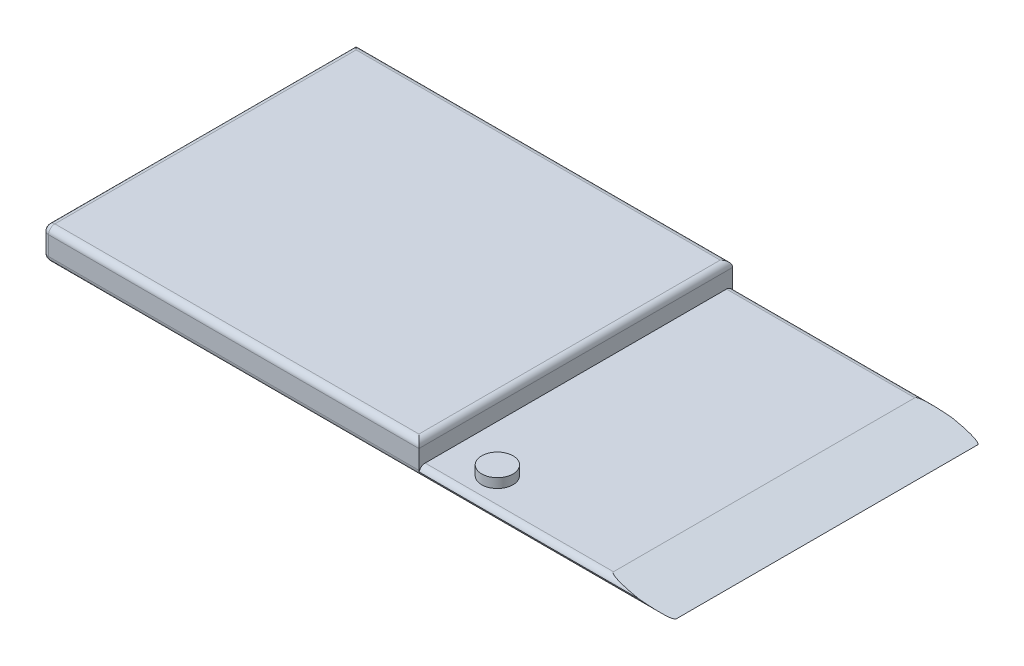
SolidWorks part; units mm, degrees
ref_plane "Front Plane" through (0, 0, 0) normal (0, 0, 1) x (1, 0, 0)
ref_plane "Top Plane" through (0, 0, 0) normal (0, 1, 0) x (1, 0, 0)
ref_plane "Right Plane" through (0, 0, 0) normal (1, 0, 0) x (0, 0, -1)
sketch "Sketch1" plane through (0, 0, 0) normal (0, 1, 0) x (1, 0, 0)
  line L1 (-127, 63.5) -> (127, 63.5)
  line L2 (-127, 63.5) -> (-127, -63.5)
  line L3 (-127, -63.5) -> (127, -63.5)
  line L4 (127, 63.5) -> (127, -63.5)
  line L5 (-127, 63.5) -> (127, -63.5) construction
  line L6 (-127, -63.5) -> (127, 63.5) construction
  point P0 (0, 0)
  dimension "D1" = 254
  dimension "D2" = 127
extrude "Boss-Extrude1" add sketch "Sketch1" along normal blind 12.7
sketch "Sketch2" plane through (0, 0, 63.5) normal (0, 0, 1) x (1, 0, 0)
  line L0 (25.4, 12.7) -> (25.4, 3.81)
  line L1 (-127, 12.7) -> (127, 12.7) construction
  line L2 (25.4, 3.81) -> (101.6, 3.81)
  line L3 (101.6, 3.81) -> (127, 0)
  line L8 (-127, 0) -> (127, 0)
  line L9 (127, 0) -> (127, 12.7)
  line L10 (127, 12.7) -> (-127, 12.7)
  line L11 (-127, 12.7) -> (-127, 0)
  line L12 (-127, 0) -> (127, 0)
  line L14 (25.4, 12.7) -> (-127, 12.7)
  line L15 (-127, 12.7) -> (-127, 0)
  dimension "D1" = 0
extrude "Cut-Extrude2" cut sketch "Sketch2" against normal through all flip side to cut
fillet "Fillet1" radius 2.54 4 edges at (25.4, 12.7, 0) (-50.8, 12.7, -63.5) (-127, 12.7, 0) (-50.8, 12.7, 63.5)
fillet "Fillet4" radius 2.54 3 edges at (63.5, 3.81, -63.5) (63.5, 3.81, 63.5) (0, 0, 63.5)
fillet "Fillet5" radius 2.54 5 edges at (-126.2561, 11.9561, 62.7561) (-127, 6.35, 63.5) (-127, 0.7439, 62.7561) (-127, 0, -1.27) (0, 0, -63.5)
sketch "Sketch3" plane through (0, 3.81, 0) normal (0, 1, 0) x (1, 0, 0)
  circle A0 centre (44.45, -50.8) radius 6.35
extrude "Boss-Extrude2" add sketch "Sketch3" along normal blind 3.81
